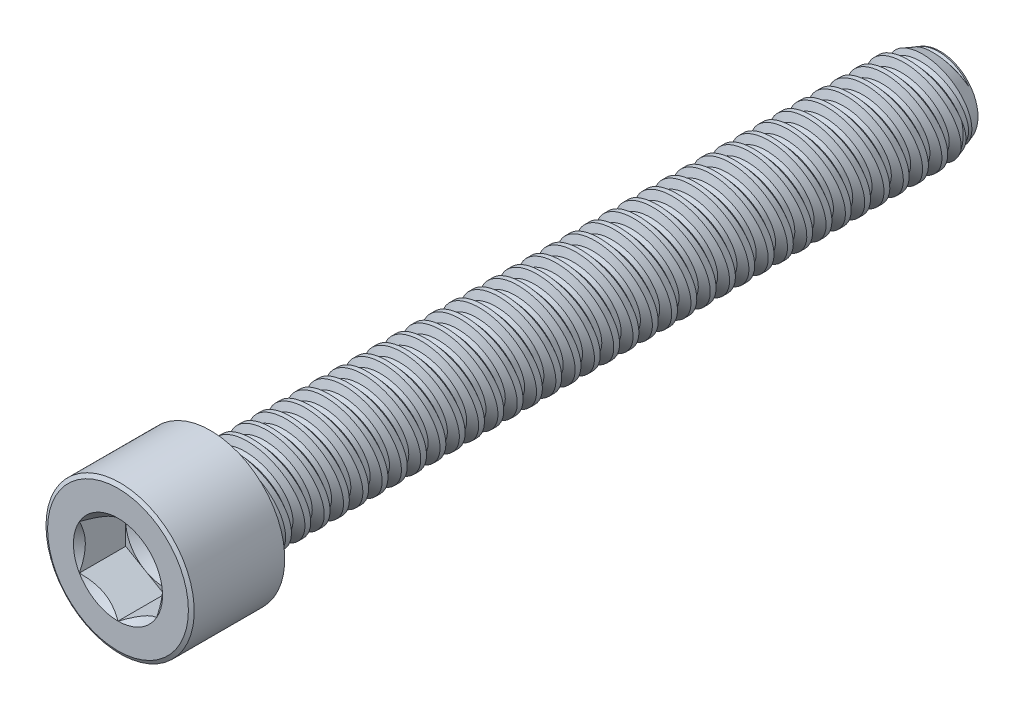
SolidWorks part; units mm, degrees
ref_plane "Front" through (0, 0, 0) normal (0, 0, 1) x (1, 0, 0)
ref_plane "Top" through (0, 0, 0) normal (0, 1, 0) x (1, 0, 0)
ref_plane "Right" through (0, 0, 0) normal (1, 0, 0) x (0, 0, -1)
sketch "Sketch1" plane through (0, 0, 0) normal (1, 0, 0) x (0, 0, -1)
  line L0 (0, 0) -> (-1.2, 0) construction
  line L1 (0, 0) -> (12, 0)
  line L2 (0, 0) -> (0, 0.762)
  line L3 (0, 0.762) -> (12, 0.762)
  line L4 (12, 0) -> (12, 0.762)
  line L5 (0, -0.762) -> (12, -0.762) construction
  dimension "D1" = 1.2
  dimension "Thread Dia" = 1.524
  dimension "Screw Length" = 12
revolve "Revolve1" add sketch "Sketch1" angle 360 about L0
sketch "Sketch2" plane through (0, 0, 0) normal (1, 0, 0) x (0, 0, -1)
  line L0 (0, 0.762) -> (0, -0.762) construction
  line L1 (0, -0.762) -> (0.3175, -0.762) construction
  line L2 (0.3175, -0.762) -> (0, 0.762) construction
  line L3 (0, 0.762) -> (0.0389, 0.7701) construction
  line L4 (0.0389, 0.7701) -> (0.3108, 0.8268)
  line L5 (0.3108, 0.8268) -> (0.2487, 0.6383)
  line L6 (0.2487, 0.6383) -> (0.171, 0.6221)
  line L7 (0.171, 0.6221) -> (0.0389, 0.7701)
  line L8 (0.2099, 0.6302) -> (0.1748, 0.7984) construction
  line L9 (0, -0.762) -> (12, -0.762) construction
  line L10 (0, 0.762) -> (12, 0.762) construction
  line L12 (0.1824, 0.762) -> (0.4999, -0.762) construction
  line L13 (0, -0.0711) -> (0.6824, 0.0711) construction
  line L15 (0, 0) -> (0, 0.762) construction
  point P19 (0.3412, 0)
  dimension "D1" = 60
  dimension "Thread Pitch" = 0.3175
  dimension "D2" = 0.0397
  dimension "D3" = 0.0794
  dimension "D4" = 0.3175
revolve "Cut-Revolve1" cut sketch "Sketch2" angle 360 about L13
sketch "Sketch3" plane through (0, 0, 0) normal (1, 0, 0) x (0, 0, -1)
  line L0 (12, 0.6221) -> (11.6156, 0.762)
  line L1 (11.6156, 0.762) -> (12, 0.762)
  line L2 (12, 0.762) -> (12, 0.6221)
  line L3 (0, 0.762) -> (12, 0.762) construction
  line L4 (12, 0) -> (12, 0.762) construction
  line L5 (11.6156, 0) -> (0, 0) construction
  line L6 (11.6156, 0.762) -> (11.6156, -0.762) construction
  line L7 (0, -0.762) -> (12, -0.762) construction
  dimension "D1" = 20
  dimension "D2" = 1.524
revolve "Cut-Revolve2" cut sketch "Sketch3" angle 360 about L5
pattern_linear "LPattern1" count 38 spacing 0.3175 along (0, 0, -1) of "Cut-Revolve1"
pattern_linear "LPattern2" count 2 spacing 0.3175 along (0, 0, 1) of "Cut-Revolve1"
sketch "Sketch4" plane through (0, 0, 0) normal (0, 0, 1) x (1, 0, 0)
  circle A0 centre (0, 0) radius 1.2192
  dimension "Head Dia" = 2.4384
extrude "Extrude1" add sketch "Sketch4" along normal blind 1.524
chamfer "Chamfer1" distance 0.061 angle 30 1 edges at (1.2192, 0, 1.524) first distance on face at (1.2192, 0, 1.524)
sketch "Sketch6" plane through (0, 0, 1.524) normal (0, 0, 1) x (1, 0, 0)
  line L1 (0, -0.7332) -> (0.635, -0.3666)
  line L2 (0.635, -0.3666) -> (0.635, 0.3666)
  line L3 (0.635, 0.3666) -> (0, 0.7332)
  line L4 (0, 0.7332) -> (-0.635, 0.3666)
  line L5 (-0.635, 0.3666) -> (-0.635, -0.3666)
  line L6 (-0.635, -0.3666) -> (0, -0.7332)
  circle A0 centre (0, 0) radius 0.635 construction
  dimension "Hex" = 1.27
extrude "Cut-Extrude1" cut sketch "Sketch6" against normal blind 0.762
sketch "Sketch7" plane through (0, 0, 1.524) normal (0, 0, 1) x (1, 0, 0)
  circle A0 centre (0, 0) radius 0.7332
extrude "Cut-Extrude4" cut sketch "Sketch7" against normal blind 0.762 draft 45
sketch "Sketch8" plane through (0, 0, 0.762) normal (0, 0, 1) x (1, 0, 0)
  circle A0 centre (0, 0) radius 0.635 construction
  circle A1 centre (0, 0) radius 0.635
extrude "Cut-Extrude5" cut sketch "Sketch8" against normal blind 0.254 draft 60
equation "\"D1@Sketch1\"=\"Screw Length@Sketch1\"/10"
equation "\"D2@Sketch2\"=\"Thread Pitch@Sketch2\"/8"
equation "\"D3@Sketch2\"=\"Thread Pitch@Sketch2\"/4"
equation "\"D4@Sketch2\"=\"Thread Pitch@Sketch2\""
equation "\"D3@LPattern1\"=\"Thread Pitch@Sketch2\""
equation "\"D1@Chamfer1\"=\"Thread Dia@Sketch1\"/25"
equation "\"D1@Cut-Extrude1\"=\"Head Height@Extrude1\"/2"
equation "\"D1@Cut-Extrude4\"=\"D1@Cut-Extrude1\""
equation "\"D1@Cut-Extrude5\"=\"D1@Cut-Extrude1\"/3"
equation "\"D1@LPattern1\"=\"Screw Length@Sketch1\"/\"Thread Pitch@Sketch2\""
equation "\"D3@LPattern2\"=\"Thread Pitch@Sketch2\""
